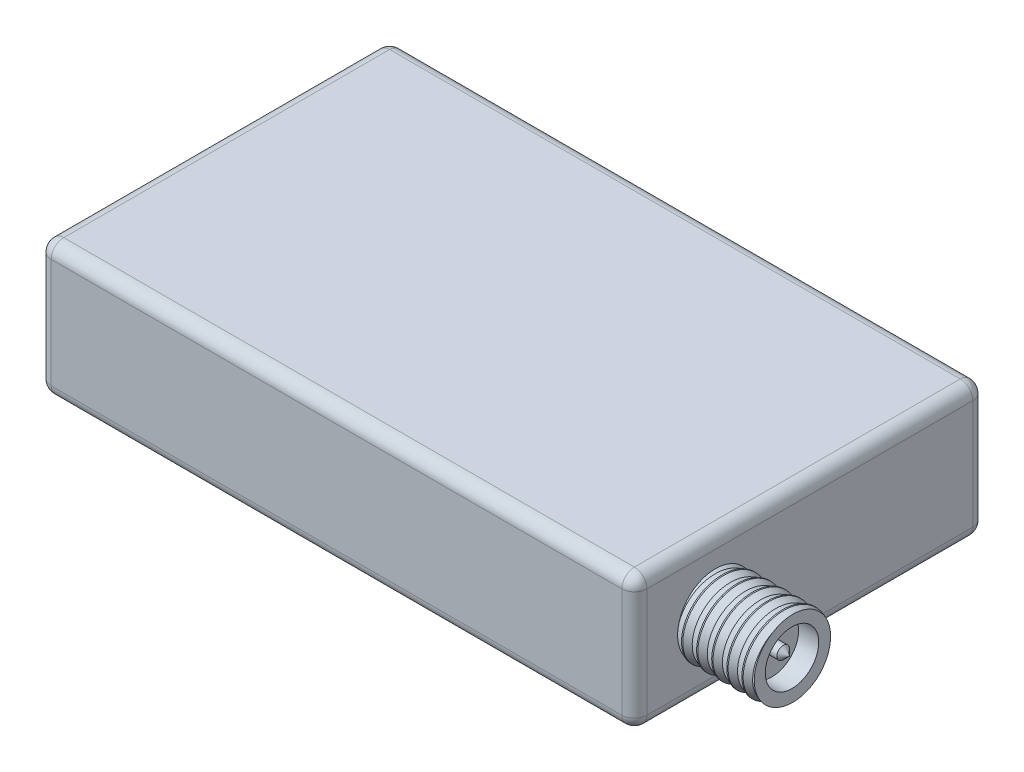
SolidWorks part; units mm, degrees
ref_plane "Front Plane" through (0, 0, 0) normal (0, 0, 1) x (1, 0, 0)
ref_plane "Top Plane" through (0, 0, 0) normal (0, 1, 0) x (1, 0, 0)
ref_plane "Right Plane" through (0, 0, 0) normal (1, 0, 0) x (0, 0, -1)
sketch "Sketch1" plane through (0, 0, 0) normal (0, 1, 0) x (1, 0, 0)
  line L0 (-55, 0) -> (55, 0) construction
  line L1 (-23.68, 13.95) -> (23.68, 13.95)
  line L2 (-23.68, 13.95) -> (-23.68, -13.95)
  line L3 (-23.68, -13.95) -> (23.68, -13.95)
  line L4 (23.68, 13.95) -> (23.68, -13.95)
  line L6 (0, -55) -> (0, 55) construction
  point P4 (23.68, 0)
  point P8 (0, 13.95)
  dimension "D1" = 47.36
  dimension "D2" = 27.9
extrude "Boss-Extrude1" add sketch "Sketch1" along normal mid plane 10.7
sketch "Sketch2" plane through (23.68, 0, 0) normal (1, 0, 0) x (0, 0, -1)
  line L0 (-13.95, 5.35) -> (-13.95, -5.35) construction
  line L1 (15.345, 0) -> (-15.345, 0) construction
  circle A0 centre (-7.575, 0) radius 3.125
  dimension "D1" = 6.25
  dimension "D2" = 6.375
extrude "Boss-Extrude2" add sketch "Sketch2" along normal blind 6.15
sketch "Sketch3" plane through (-23.68, 0, 0) normal (-1, 0, 0) x (0, 0, 1)
  line L0 (-13.95, -5.35) -> (13.95, -5.35) construction
  line L1 (-10.25, 0.95) -> (0.95, 0.95)
  line L2 (-10.25, 0.95) -> (-10.25, -4.05)
  line L3 (-10.25, -4.05) -> (0.95, -4.05)
  line L4 (0.95, 0.95) -> (0.95, -4.05)
  line L5 (-13.95, 5.35) -> (-13.95, -5.35) construction
  dimension "D1" = 11.2
  dimension "D2" = 1.3
  dimension "D3" = 3.7
  dimension "D4" = 5
extrude "Cut-Extrude1" cut sketch "Sketch3" against normal blind 7
sketch "Sketch5" plane through (-23.68, 0, 0) normal (-1, 0, 0) x (0, 0, 1)
  line L1 (0.95, 0.95) -> (9.85, 0.95)
  line L2 (0.95, 0.95) -> (0.95, -2.25)
  line L3 (0.95, -2.25) -> (9.85, -2.25)
  line L4 (9.85, 0.95) -> (9.85, -2.25)
  dimension "D1" = 3.2
  dimension "D2" = 8.9
extrude "Cut-Extrude2" cut sketch "Sketch5" against normal blind 6
sketch "Sketch6" plane through (29.83, 0, 0) normal (1, 0, 0) x (0, 0, -1)
  line L0 (15.345, 0) -> (-15.345, 0) construction
  circle A0 centre (-7.575, 0) radius 2.125
  circle A1 centre (-7.575, 0) radius 3.125 construction
  dimension "D1" = 1
extrude "Cut-Extrude3" cut sketch "Sketch6" against normal blind 1.6
sketch "Sketch7" plane through (28.23, 0, 0) normal (1, 0, 0) x (0, 0, -1)
  circle A0 centre (-7.575, 0) radius 0.5
  circle A1 centre (-7.575, 0) radius 2.125 construction
  dimension "D1" = 1
extrude "Boss-Extrude3" add sketch "Sketch7" along normal blind 1.4
chamfer "Chamfer1" distance 0.5 angle 45 1 edges at (29.63, 0, 7.075)
sketch "Sketch8" plane through (23.68, 0, 0) normal (1, 0, 0) x (0, 0, -1)
  circle A0 centre (-7.575, 0) radius 3.125 construction
  circle A1 centre (-7.575, 0) radius 3.125
curve "Helix/Spiral1" pitch 1.2 height 7.2 radius 3.125 left hand yes centre (23.68, 0, 7.575) axis (1, 0, 0) start towards (0, 0, -1)
sketch "Sketch9" plane through (0, 0, 0) normal (0, 1, 0) x (1, 0, 0)
  line L0 (23.68, -4.45) -> (24.23, -4.65)
  line L1 (29.83, -4.45) -> (23.68, -4.45) construction
  line L2 (24.23, -4.65) -> (24.78, -4.45)
  line L3 (24.78, -4.45) -> (23.68, -4.45)
  spline S0 degree 3 poles (23.68, -4.45) (23.7048, -4.45) (23.7551, -4.6127) (23.83, -5.3078) (23.905, -6.348) (23.98, -7.575) (24.055, -8.802) (24.13, -9.8422) (24.205, -10.5373) (24.28, -10.7814) (24.355, -10.5373) (24.43, -9.8422) (24.53, -8.4553) (24.63, -6.6947) (24.73, -5.3078) (24.805, -4.6127) (24.88, -4.3686) (24.955, -4.6127) (25.03, -5.3078) (25.13, -6.6947) (25.23, -8.4553) (25.33, -9.8422) (25.405, -10.5373) (25.48, -10.7814) (25.555, -10.5373) (25.63, -9.8422) (25.73, -8.4553) (25.83, -6.6947) (25.93, -5.3078) (26.005, -4.6127) (26.08, -4.3686) (26.155, -4.6127) (26.23, -5.3078) (26.33, -6.6947) (26.43, -8.4553) (26.53, -9.8422) (26.605, -10.5373) (26.68, -10.7814) (26.755, -10.5373) (26.83, -9.8422) (26.93, -8.4553) (27.03, -6.6947) (27.13, -5.3078) (27.205, -4.6127) (27.28, -4.3686) (27.355, -4.6127) (27.43, -5.3078) (27.53, -6.6947) (27.63, -8.4553) (27.73, -9.8422) (27.805, -10.5373) (27.88, -10.7814) (27.955, -10.5373) (28.03, -9.8422) (28.13, -8.4553) (28.23, -6.6947) (28.33, -5.3078) (28.405, -4.6127) (28.48, -4.3686) (28.555, -4.6127) (28.63, -5.3078) (28.73, -6.6947) (28.83, -8.4553) (28.93, -9.8422) (29.005, -10.5373) (29.08, -10.7814) (29.155, -10.5373) (29.23, -9.8422) (29.33, -8.4553) (29.43, -6.6947) (29.53, -5.3078) (29.605, -4.6127) (29.68, -4.3686) (29.755, -4.6127) (29.83, -5.3078) (29.93, -6.6947) (30.03, -8.4553) (30.13, -9.8422) (30.205, -10.5373) (30.28, -10.7814) (30.355, -10.5373) (30.43, -9.8422) (30.505, -8.802) (30.58, -7.575) (30.655, -6.348) (30.73, -5.3078) (30.8049, -4.6127) (30.8552, -4.45) (30.88, -4.45) knots 0 0 0 0 0.010417 0.020833 0.03125 0.041667 0.052083 0.0625 0.072917 0.083333 0.09375 0.104167 0.114583 0.135417 0.145833 0.15625 0.166667 0.177083 0.1875 0.197917 0.21875 0.229167 0.239583 0.25 0.260417 0.270833 0.28125 0.302083 0.3125 0.322917 0.333333 0.34375 0.354167 0.364583 0.385417 0.395833 0.40625 0.416667 0.427083 0.4375 0.447917 0.46875 0.479167 0.489583 0.5 0.510417 0.520833 0.53125 0.552083 0.5625 0.572917 0.583333 0.59375 0.604167 0.614583 0.635417 0.645833 0.65625 0.666667 0.677083 0.6875 0.697917 0.71875 0.729167 0.739583 0.75 0.760417 0.770833 0.78125 0.802083 0.8125 0.822917 0.833333 0.84375 0.854167 0.864583 0.885417 0.895833 0.90625 0.916667 0.927083 0.9375 0.947917 0.958333 0.96875 0.979167 0.989583 1 1 1 1 construction
  dimension "D1" = 0.2
  dimension "D2" = 1.1
sweep "Cut-Sweep1" cut profiles "Sketch9" path "Helix/Spiral1" align with end faces yes
sketch "Sketch11" plane through (-16.68, 0, 0) normal (-1, 0, 0) x (0, 0, 1)
  line L1 (-10.025, 0.575) -> (0.725, 0.575)
  line L2 (-10.025, 0.575) -> (-10.025, -3.675)
  line L3 (-10.025, -3.675) -> (0.725, -3.675)
  line L4 (0.725, 0.575) -> (0.725, -3.675)
  line L10 (-10.25, 0.95) -> (-10.25, -4.05)
  line L11 (-10.25, -4.05) -> (0.95, -4.05)
  line L12 (0.95, -4.05) -> (0.95, 0.95)
  line L15 (0.95, 0.95) -> (-10.25, 0.95)
  line L16 (-10.25, 0.95) -> (-10.25, -4.05)
  line L17 (-10.25, -4.05) -> (0.95, -4.05)
  line L18 (0.95, -4.05) -> (0.95, 0.95)
  line L21 (0.95, 0.95) -> (-10.25, 0.95)
  point P8 (-4.65, -3.675)
  point P10 (-4.65, 0.95)
  point P12 (-10.025, -1.55)
  point P14 (-10.25, -1.55)
  dimension "D1" = 10.75
  dimension "D2" = 4.25
  dimension "D3" = 0
extrude "Boss-Extrude5" add sketch "Sketch11" along normal up to surface (7 mm away) up to face at (-23.68, -1.7833, 0.1833)
sketch "Sketch12" plane through (-17.68, 0, 0) normal (-1, 0, 0) x (0, 0, 1)
  line L0 (-10.025, 0.575) -> (0.725, 0.575) construction
  line L1 (1.65, 0.575) -> (9.15, 0.575)
  line L2 (1.65, 0.575) -> (1.65, -1.875)
  line L3 (1.65, -1.875) -> (9.15, -1.875)
  line L4 (9.15, 0.575) -> (9.15, -1.875)
  line L10 (0.95, 0.95) -> (0.95, -2.25)
  line L11 (0.95, -2.25) -> (9.85, -2.25)
  line L12 (9.85, -2.25) -> (9.85, 0.95)
  line L13 (9.85, 0.95) -> (0.95, 0.95)
  line L14 (0.95, 0.95) -> (0.95, -2.25)
  line L15 (0.95, -2.25) -> (9.85, -2.25)
  line L16 (9.85, -2.25) -> (9.85, 0.95)
  line L17 (9.85, 0.95) -> (0.95, 0.95)
  point P8 (5.4, 0.95)
  point P10 (5.4, 0.575)
  dimension "D1" = 7.5
  dimension "D2" = 2.45
  dimension "D3" = 0
extrude "Boss-Extrude6" add sketch "Sketch12" along normal up to surface (6 mm away) up to face at (-23.68, -0.65, 5.4)
fillet "Fillet1" radius 1 12 edges at (0, -5.35, 13.95) (23.68, -5.35, 0) (0, -5.35, -13.95) (-23.68, -5.35, 0) (0, 5.35, -13.95) (23.68, 5.35, 0) (0, 5.35, 13.95) (-23.68, 5.35, 0) (23.68, 0, 13.95) (23.68, 0, -13.95) (-23.68, 0, 13.95) (-23.68, 0, -13.95)
